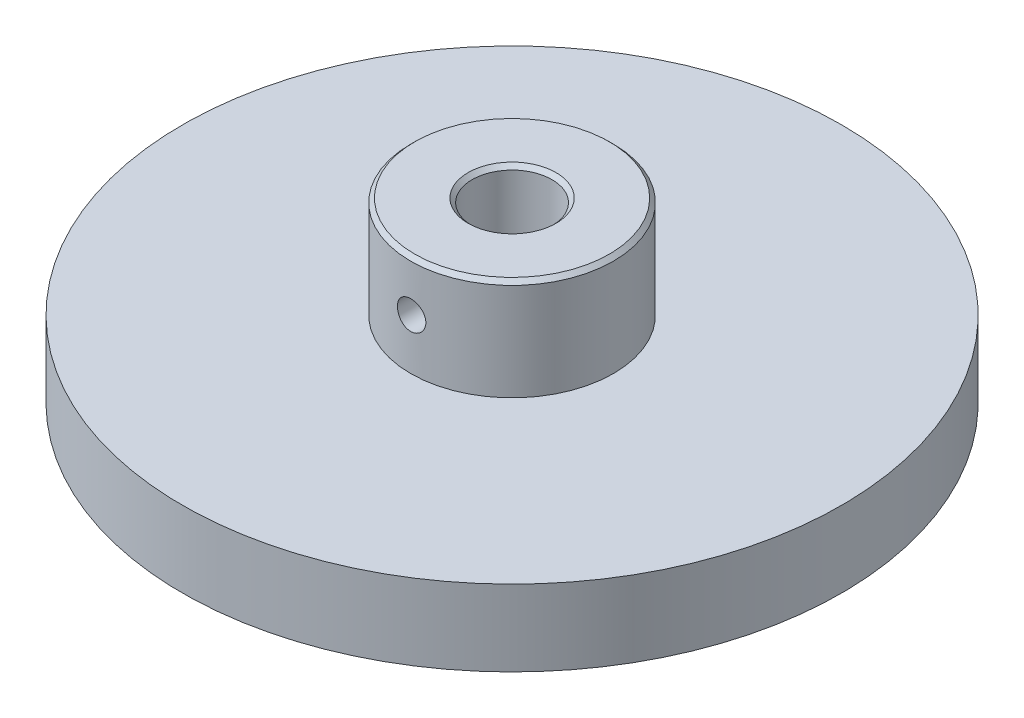
SolidWorks part; units mm, degrees
material "Nylon 6/10"
ref_plane "Front Plane" through (0, 0, 0) normal (0, 0, 1) x (1, 0, 0)
ref_plane "Top Plane" through (0, 0, 0) normal (0, 1, 0) x (1, 0, 0)
ref_plane "Right Plane" through (0, 0, 0) normal (1, 0, 0) x (0, 0, -1)
sketch "Sketch1" plane through (0, 0, 0) normal (0, 1, 0) x (1, 0, 0)
  circle A0 centre (0, 0) radius 20.6375
  dimension "D1" = 41.275
extrude "Boss-Extrude1" add sketch "Sketch1" along normal blind 4.7625
sketch "Sketch2" plane through (0, 4.7625, 0) normal (0, 1, 0) x (1, 0, 0)
  circle A0 centre (0, 0) radius 6.35
  dimension "D1" = 12.7
extrude "Boss-Extrude2" add sketch "Sketch2" along normal blind 6.35
sketch "Sketch3" plane through (0, 0, 0) normal (0, -1, 0) x (1, 0, 0)
  circle A0 centre (0, 0) radius 2.5
  dimension "D1" = 5
extrude "Cut-Extrude1" cut sketch "Sketch3" against normal through all
chamfer "Chamfer1" distance 0.254 angle 45 3 edges at (0, 0, -2.5) (0, 11.1125, -2.5) (0, 11.1125, 6.35)
hole_wizard "#2-56 Tapped Hole1" positions "Sketch6" profile "Sketch5" tap size "#2-56" standard "ANSI Inch" end condition through all
sketch "Sketch6" plane through (0, 0, 0) normal (0, 0, 1) x (1, 0, 0)
  line L0 (6.35, 4.7625) -> (-6.35, 4.7625) construction
  point P0 (0, 7.9375)
  dimension "D1" = 3.175
sketch "Sketch5" plane through (0, 7.9375, 0) normal (1, 0, 0) x (0, 1, 0)
  line L0 (0, 0) -> (0, 20.6375)
  line L1 (0, 20.6375) -> (0.889, 20.6375)
  line L2 (0.889, 20.6375) -> (0.889, 0)
  line L5 (0.889, 0) -> (0, 0)
  line L11 (0, -6.35) -> (0, 107.95) construction
  dimension "Thru Tap Drill Dia." = 1.778
  dimension "Thru Tap Drill Depth" = 20.6375
cosmetic thread "Hole Thread1" parameters "D2"=2.1844
